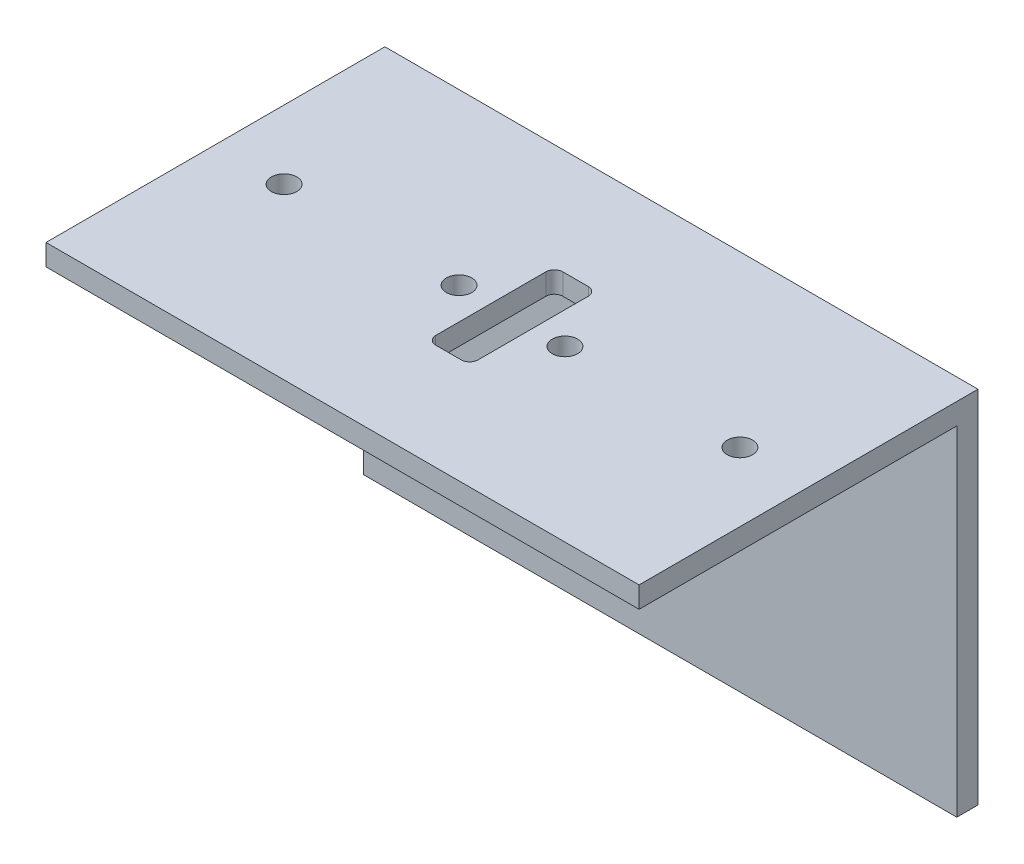
SolidWorks part; units mm, degrees
ref_plane "Front Plane" through (0, 0, 0) normal (0, 0, 1) x (1, 0, 0)
ref_plane "Top Plane" through (0, 0, 0) normal (0, 1, 0) x (1, 0, 0)
ref_plane "Right Plane" through (0, 0, 0) normal (1, 0, 0) x (0, 0, -1)
sketch "Sketch1" plane through (0, 0, 0) normal (0, 1, 0) x (1, 0, 0)
  line L0 (0, 18.2197) -> (0, -18.3609) construction
  line L1 (-19.3496, 0) -> (20.197, 0) construction
  line L2 (-33.15, 0) -> (-33.15, -10) construction
  line L3 (70, 40) -> (-70, 40)
  line L4 (-70, 40) -> (-70, -40)
  line L5 (70, -40) -> (-70, -40)
  line L6 (70, 40) -> (70, -40)
  line L7 (5, 15) -> (-5, 15)
  line L8 (-5, 15) -> (-5, -15)
  line L9 (5, -15) -> (-5, -15)
  line L10 (5, 15) -> (5, -15)
  circle A0 centre (-33.15, 0) radius 10 construction
  circle A1 centre (-12.5, 0) radius 3.4 construction
  circle A2 centre (-53.8, 0) radius 3.4 construction
  circle A3 centre (-12.5, 0) radius 3
  circle A4 centre (-53.8, 0) radius 3
  circle A5 centre (53.8, 0) radius 3
  circle A6 centre (53.8, 0) radius 3.4 construction
  circle A7 centre (33.15, 0) radius 10 construction
  circle A8 centre (12.5, 0) radius 3.4 construction
  circle A9 centre (12.5, 0) radius 3
  point P18 (-70, 0)
  point P20 (0, 40)
  point P21 (0, -40)
  point P33 (-5, 0)
  point P35 (0, -15)
  point P36 (0, 15)
  dimension "D1" = 20
  dimension "D3" = 6.8
  dimension "D4" = 41.3
  dimension "D5" = 6
  dimension "D2" = 25
  dimension "D6" = 140
  dimension "D7" = 80
  dimension "D8" = 10
  dimension "D9" = 30
extrude "Boss-Extrude1" add sketch "Sketch1" along normal blind 5
fillet "Fillet1" radius 2 4 edges at (5, 2.5, 15) (-5, 2.5, 15) (5, 2.5, -15) (-5, 2.5, -15)
sketch "Sketch2" plane through (0, 0, 0) normal (0, -1, 0) x (1, 0, 0)
  line L0 (-70, -40) -> (-70, -35)
  line L1 (-70, -40) -> (-70, 40) construction
  line L2 (-70, -35) -> (70, -35)
  line L3 (70, 40) -> (70, -40) construction
  line L4 (70, -35) -> (70, -40)
  line L5 (70, -40) -> (-70, -40)
  dimension "D1" = 5
extrude "Boss-Extrude2" add sketch "Sketch2" along normal blind 80
